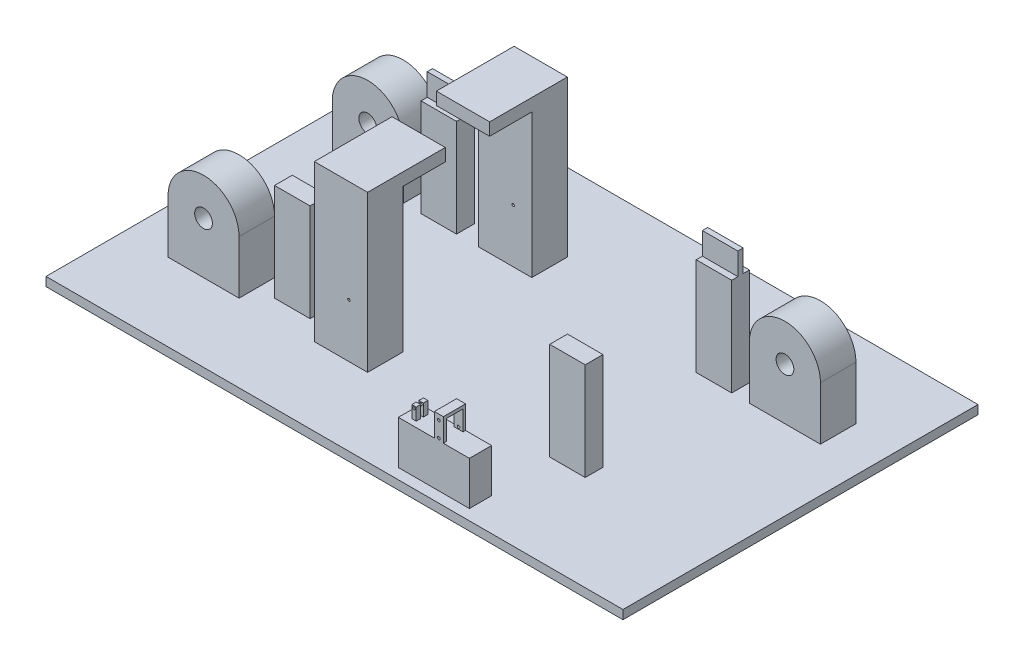
SolidWorks part; units mm, degrees
ref_plane "Plan de face" through (0, 0, 0) normal (0, 0, 1) x (1, 0, 0)
ref_plane "Plan de dessus" through (0, 0, 0) normal (0, 1, 0) x (1, 0, 0)
ref_plane "Plan de droite" through (0, 0, 0) normal (1, 0, 0) x (0, 0, -1)
sketch "Esquisse2" plane through (0, 0, 0) normal (0, 1, 0) x (1, 0, 0)
  line L1 (-325, 200) -> (325, 200)
  line L2 (-325, 200) -> (-325, -200)
  line L3 (-325, -200) -> (325, -200)
  line L4 (325, 200) -> (325, -200)
  line L5 (-325, 200) -> (325, -200) construction
  line L6 (-325, -200) -> (325, 200) construction
  point P0 (0, 0)
  dimension "D1" = 650
  dimension "D2" = 400
extrude "Boss.-Extru.1" add sketch "Esquisse2" along normal mid plane 10
sketch "Esquisse3" plane through (0, 5, 0) normal (0, 1, 0) x (1, 0, 0)
  line L12 (-275, -72.5) -> (-195, -72.5)
  line L13 (-275, -72.5) -> (-275, -112.5)
  line L14 (-275, -112.5) -> (-195, -112.5)
  line L15 (-195, -72.5) -> (-195, -112.5)
  line L16 (-275, -72.5) -> (-195, -112.5) construction
  line L17 (-275, -112.5) -> (-195, -72.5) construction
  line L19 (195, 112.5) -> (275, 112.5)
  line L20 (195, 112.5) -> (195, 72.5)
  line L21 (195, 72.5) -> (275, 72.5)
  line L22 (275, 112.5) -> (275, 72.5)
  line L23 (195, 112.5) -> (275, 72.5) construction
  line L24 (195, 72.5) -> (275, 112.5) construction
  line L26 (-275, 112.5) -> (-195, 112.5)
  line L27 (-275, 112.5) -> (-275, 72.5)
  line L28 (-275, 72.5) -> (-195, 72.5)
  line L29 (-195, 112.5) -> (-195, 72.5)
  line L30 (-275, 112.5) -> (-195, 72.5) construction
  line L31 (-275, 72.5) -> (-195, 112.5) construction
  point P0 (-235, -92.5)
  point P9 (-195, -92.5)
  point P10 (235, 92.5)
  point P19 (-235, 92.5)
  dimension "D1" = 145
  dimension "D2" = 72.5
  dimension "D3" = 40
  dimension "D4" = 80
  dimension "D5" = 72.5
  dimension "D6" = 195
  dimension "D7" = 40
  dimension "D8" = 80
  dimension "D9" = 275
extrude "Boss.-Extru.3" add sketch "Esquisse3" along normal blind 100
fillet "Congé2" 2 edges at (-275, 105, 92.5) (-195, 105, 92.5) type full round first side face at (-275, 55, 92.5) second side face at (-195, 55, 92.5) middle face at (-235, 105, 92.5)
fillet "Congé3" 2 edges at (-275, 105, -92.5) (-195, 105, -92.5) type full round first side face at (-275, 55, -92.5) second side face at (-195, 55, -92.5) middle face at (-235, 105, -92.5)
fillet "Congé4" 2 edges at (195, 105, -92.5) (275, 105, -92.5) type full round first side face at (195, 55, -92.5) second side face at (275, 55, -92.5) middle face at (235, 105, -92.5)
sketch "Esquisse6" plane through (0, 0, 112.5) normal (0, 0, 1) x (1, 0, 0)
  line L4 (-275, 65) -> (-275, 5) construction
  circle A0 centre (-235, 63) radius 10
  dimension "D2" = 40
  dimension "D1" = 20
extrude "Enlèv. mat.-Extru.2" cut sketch "Esquisse6" against normal through all
sketch "Esquisse7" plane through (0, 0, -112.5) normal (0, 0, -1) x (-1, 0, 0)
  line L0 (-275, 5) -> (-195, 5) construction
  line L1 (-275, 65) -> (-275, 5) construction
  circle A0 centre (-235, 63) radius 10
  dimension "D1" = 58
  dimension "D3" = 20
  dimension "D2" = 40
extrude "Enlèv. mat.-Extru.3" cut sketch "Esquisse7" against normal through all contours A0
sketch "Esquisse8" plane through (0, 5, 0) normal (0, 1, 0) x (1, 0, 0)
  line L0 (-318.535, 0) -> (313.432, 0) construction
  line L1 (-2.5515, 193.1003) -> (-2.5515, -193.2582) construction
sketch "Esquisse9" plane through (0, 5, 0) normal (0, 1, 0) x (1, 0, 0)
  line L0 (325, -200) -> (325, 200) construction
  line L1 (60, -163) -> (140, -163)
  line L2 (60, -163) -> (60, -188)
  line L3 (60, -188) -> (140, -188)
  line L4 (140, -163) -> (140, -188)
  line L5 (60, -163) -> (140, -188) construction
  line L6 (60, -188) -> (140, -163) construction
  line L7 (-325, -200) -> (325, -200) construction
  point P0 (100, -175.5)
  dimension "D1" = 185
  dimension "D2" = 25
  dimension "D3" = 80
  dimension "D4" = 12
extrude "Boss.-Extru.4" add sketch "Esquisse9" along normal blind 49
sketch "Esquisse10" plane through (0, 54, 0) normal (0, 1, 0) x (1, 0, 0)
  line L0 (60, -188) -> (140, -188) construction
  line L1 (110.67, -188) -> (100.57, -188)
  line L2 (110.67, -188) -> (110.67, -184.6)
  line L3 (110.67, -184.6) -> (100.57, -184.6)
  line L4 (100.57, -188) -> (100.57, -184.6)
  line L5 (140, -188) -> (140, -163) construction
  dimension "D1" = 29.33
  dimension "D2" = 10.1
  dimension "D3" = 3.4
extrude "Boss.-Extru.5" add sketch "Esquisse10" along normal blind 26
sketch "Esquisse11" plane through (0, 0, 188) normal (0, 0, 1) x (1, 0, 0)
  line L0 (60, 54) -> (100.57, 54) construction
  line L1 (110.67, 80) -> (110.67, 54) construction
  circle A0 centre (105.62, 56.5) radius 1.5
  circle A1 centre (105.62, 74) radius 1.5
  point P10 (0, 0)
  dimension "D1" = 3
  dimension "D2" = 2.5
  dimension "D3" = 5.05
  dimension "D4" = 17.5
extrude "Enlèv. mat.-Extru.4" cut sketch "Esquisse11" against normal up to next
sketch "Esquisse12" plane through (0, 0, 184.6) normal (0, 0, -1) x (-1, 0, 0)
  line L0 (-100.57, 80) -> (-100.57, 54) construction
  line L1 (-110.67, 80) -> (-100.57, 80)
  line L2 (-110.67, 80) -> (-110.67, 76.5)
  line L3 (-110.67, 76.5) -> (-100.57, 76.5)
  line L4 (-100.57, 80) -> (-100.57, 76.5)
  dimension "D1" = 3.5
extrude "Boss.-Extru.6" add sketch "Esquisse12" along normal blind 21.6
sketch "Esquisse13" plane through (0, 80, 0) normal (0, 1, 0) x (1, 0, 0)
  line L0 (110.67, -188) -> (110.67, -163) construction
  line L1 (100.57, -163) -> (110.67, -163)
  line L2 (100.57, -163) -> (100.57, -165.8)
  line L3 (100.57, -165.8) -> (110.67, -165.8)
  line L4 (110.67, -163) -> (110.67, -165.8)
  dimension "D1" = 2.8
extrude "Boss.-Extru.7" add sketch "Esquisse13" against normal blind 26
sketch "Esquisse14" plane through (0, 0, 163) normal (0, 0, -1) x (-1, 0, 0)
  circle A1 centre (-105.62, 74) radius 1.5
  circle A2 centre (-105.62, 74) radius 1.5
  circle A3 centre (-105.62, 56.5) radius 1.5
  circle A4 centre (-105.62, 56.5) radius 1.5
  dimension "D1" = 0
  dimension "D2" = 0
extrude "Enlèv. mat.-Extru.5" cut sketch "Esquisse14" against normal up to next
sketch "Esquisse15" plane through (0, 54, 0) normal (0, 1, 0) x (1, 0, 0)
  line L0 (60, -188) -> (140, -188) construction
  line L1 (68.82, -176.7) -> (73.82, -176.7)
  line L2 (68.82, -176.7) -> (68.82, -181.7)
  line L3 (68.82, -181.7) -> (73.82, -181.7)
  line L4 (73.82, -176.7) -> (73.82, -181.7)
  line L5 (68.82, -168.7) -> (73.82, -168.7)
  line L6 (68.82, -168.7) -> (68.82, -173.7)
  line L7 (68.82, -173.7) -> (73.82, -173.7)
  line L8 (73.82, -168.7) -> (73.82, -173.7)
  line L9 (140, -163) -> (60, -163) construction
  line L10 (60, -163) -> (60, -188) construction
  line L11 (60, -163) -> (60, -188) construction
  dimension "D1" = 11.3
  dimension "D2" = 10.7
  dimension "D3" = 13.82
  dimension "D4" = 13.82
  dimension "D5" = 5
extrude "Boss.-Extru.8" add sketch "Esquisse15" along normal blind 13.75
sketch "Esquisse16" plane through (0, 0, 181.7) normal (0, 0, 1) x (1, 0, 0)
  line L0 (68.82, 67.75) -> (73.82, 67.75) construction
  line L1 (68.82, 67.75) -> (68.82, 54) construction
  circle A0 centre (71.22, 65.25) radius 1.4
  point P4 (0, 0)
  dimension "D1" = 2.5
  dimension "D2" = 2.8
  dimension "D3" = 2.4
extrude "Enlèv. mat.-Extru.6" cut sketch "Esquisse16" against normal through all
sketch "Esquisse17" plane through (0, 5, 0) normal (0, 1, 0) x (1, 0, 0)
  line L1 (-175, -72.5) -> (-135, -72.5)
  line L2 (-175, -72.5) -> (-175, -92.5)
  line L3 (-175, -92.5) -> (-135, -92.5)
  line L28 (-135, -72.5) -> (-135, -92.5)
  line L29 (-175, 72.5) -> (-135, 72.5)
  line L30 (-175, 72.5) -> (-175, 92.5)
  line L31 (-175, 92.5) -> (-135, 92.5)
  line L32 (-135, 72.5) -> (-135, 92.5)
  dimension "D4" = 40
  dimension "D5" = 20
  dimension "D8" = 40
  dimension "D9" = 20
extrude "Boss.-Extru.9" add sketch "Esquisse17" along normal blind 110
sketch "Esquisse18" plane through (0, 115, 0) normal (0, 1, 0) x (1, 0, 0)
  line L0 (-175, 92.5) -> (-175, 72.5) construction
  line L1 (-175, 85.5) -> (-135, 85.5)
  line L2 (-175, 85.5) -> (-175, 79.5)
  line L3 (-175, 79.5) -> (-135, 79.5)
  line L4 (-135, 85.5) -> (-135, 79.5)
  line L5 (-135, 72.5) -> (-135, 92.5) construction
  line L6 (-135, 92.5) -> (-175, 92.5) construction
  line L7 (-175, 72.5) -> (-135, 72.5) construction
  dimension "D1" = 7
  dimension "D2" = 7
extrude "Boss.-Extru.10" add sketch "Esquisse18" along normal blind 25
sketch "Esquisse20" plane through (0, 5, 0) normal (0, 1, 0) x (1, 0, 0)
  line L1 (-110.1874, -72.5) -> (-50.1874, -72.5)
  line L2 (-110.1874, -72.5) -> (-110.1874, -112.5)
  line L3 (-110.1874, -112.5) -> (-50.1874, -112.5)
  line L4 (-50.1874, -72.5) -> (-50.1874, -112.5)
  line L5 (-110.1874, 112.5) -> (-50.1874, 112.5)
  line L6 (-110.1874, 112.5) -> (-110.1874, 72.5)
  line L7 (-110.1874, 72.5) -> (-50.1874, 72.5)
  line L28 (-50.1874, 112.5) -> (-50.1874, 72.5)
  dimension "D1" = 60
  dimension "D4" = 40
extrude "Boss.-Extru.11" add sketch "Esquisse20" along normal blind 175.7
sketch "Esquisse21" plane through (0, 0, -72.5) normal (0, 0, 1) x (1, 0, 0)
  line L0 (-50.1874, 180.7) -> (-50.1874, 5) construction
  line L1 (-110.1874, 180.7) -> (-50.1874, 180.7)
  line L2 (-110.1874, 180.7) -> (-110.1874, 166.6)
  line L3 (-110.1874, 166.6) -> (-50.1874, 166.6)
  line L4 (-50.1874, 180.7) -> (-50.1874, 166.6)
  dimension "D1" = 14.1
extrude "Boss.-Extru.12" add sketch "Esquisse21" along normal up to next
sketch "Esquisse22" plane through (0, 180.7, 0) normal (0, 1, 0) x (1, 0, 0)
  line L0 (-110.1874, 112.5) -> (-110.1874, -112.5) construction
  line L1 (-110.1874, 25) -> (-50.1874, 25)
  line L2 (-110.1874, 25) -> (-110.1874, -25)
  line L3 (-110.1874, -25) -> (-50.1874, -25)
  line L4 (-50.1874, 25) -> (-50.1874, -25)
  line L5 (-50.1874, -112.5) -> (-50.1874, 112.5) construction
  line L6 (-50.1874, 112.5) -> (-110.1874, 112.5) construction
  dimension "D1" = 50
  dimension "D2" = 87.5
extrude "Enlèv. mat.-Extru.7" cut sketch "Esquisse22" against normal up to next
mirror "Symétrie1" about plane through (0, 0, 0) normal (1, 0, 0) of "Boss.-Extru.10", "Enlèv. mat.-Extru.6", "Boss.-Extru.9"
